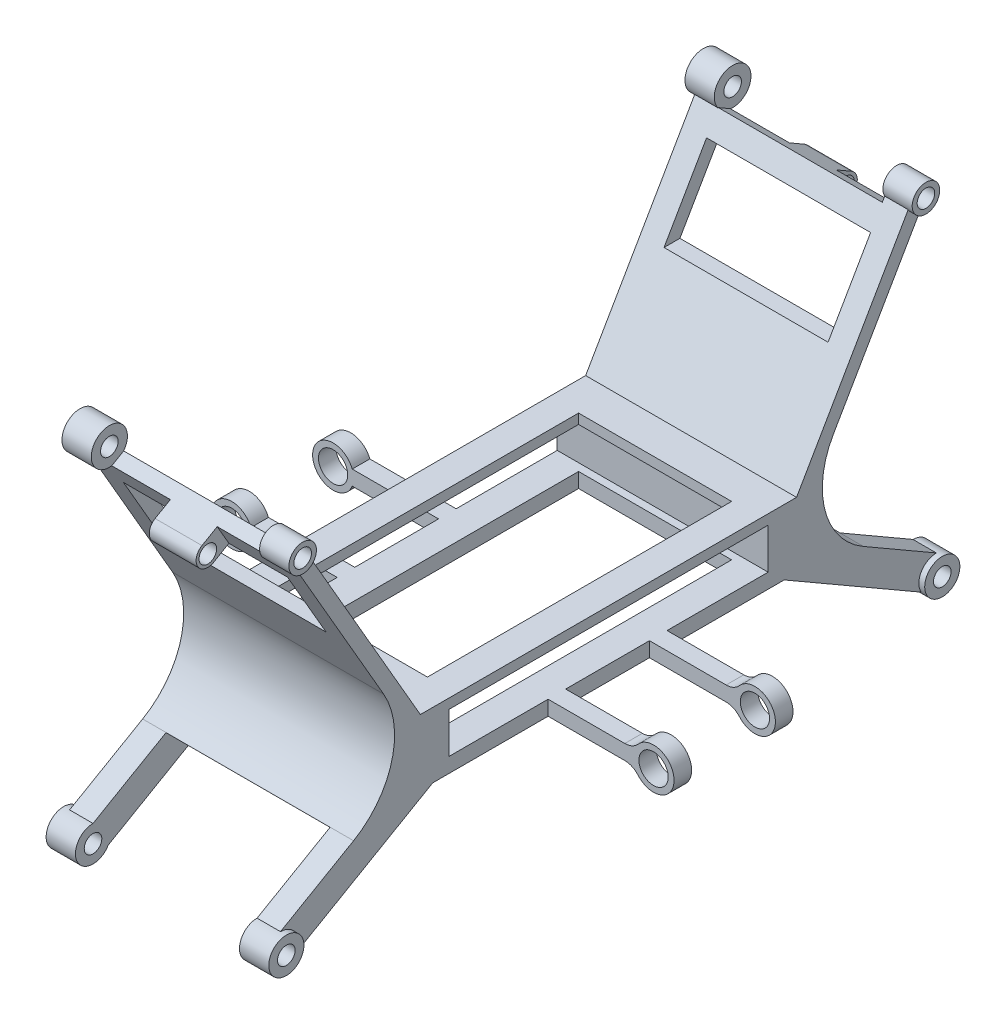
SolidWorks part; units mm, degrees
material "AISI 1020"
ref_plane "Front Plane" through (0, 0, 0) normal (0, 0, 1) x (1, 0, 0)
ref_plane "Top Plane" through (0, 0, 0) normal (0, 1, 0) x (1, 0, 0)
ref_plane "Right Plane" through (0, 0, 0) normal (1, 0, 0) x (0, 0, -1)
sketch "Sketch1" plane through (0, 0, 0) normal (1, 0, 0) x (0, 0, -1)
  line L0 (0, 0) -> (-300, 0)
  line L1 (0, 0) -> (300, 0)
  line L2 (-300, 0) -> (-559.8076, -150)
  line L3 (300, 0) -> (559.8076, -150)
  line L4 (-559.8076, -150) -> (-559.8076, -90)
  line L5 (559.8076, -150) -> (559.8076, -90)
  line L6 (-559.8076, -90) -> (-435.0569, -17.9751)
  line L7 (559.8076, -90) -> (435.0569, -17.9751)
  line L10 (-321.0542, 111.5864) -> (-531.9367, 476.8456)
  line L11 (321.0542, 111.5864) -> (531.9367, 476.8456)
  line L12 (-531.9367, 476.8456) -> (-531.9367, 429.8257)
  line L13 (-531.9367, 429.8257) -> (-383.8133, 173.2684)
  line L14 (531.9367, 476.8456) -> (531.9367, 429.8257)
  line L15 (531.9367, 429.8257) -> (383.8133, 173.2684)
  line L16 (-321.0542, 111.5864) -> (321.0542, 111.5864)
  arc A0 (435.0569, -17.9751) -> (383.8133, 173.2684) centre (505.0569, 103.2684) cw
  arc A1 (-435.0569, -17.9751) -> (-383.8133, 173.2684) centre (-505.0569, 103.2684) ccw
  point P20 (-313.8133, 52.0249)
  dimension "D12" = 140
  dimension "D19" = 0
  dimension "D1" = 300
  dimension "D2" = 300
  dimension "D3" = 300
  dimension "D4" = 300
  dimension "D5" = 30
  dimension "D6" = 30
  dimension "D7" = 60
  dimension "D8" = 60
  dimension "D9" = 60
  dimension "D10" = 51.9615
  dimension "D11" = 60
  dimension "D13" = 60
  dimension "D15" = 0
  dimension "D16" = 60
  dimension "D17" = 0
  dimension "D18" = 0
  dimension "D21" = 144.0498
extrude "Boss-Extrude2" add sketch "Sketch1" along normal blind 360
sketch "Sketch3" plane through (360, 0, 0) normal (1, 0, 0) x (0, 0, -1)
  line L1 (-272.5533, 94.7666) -> (272.5533, 94.7666)
  line L2 (-272.5533, 94.7666) -> (-272.5533, 25.2334)
  line L3 (-272.5533, 25.2334) -> (272.5533, 25.2334)
  line L4 (272.5533, 94.7666) -> (272.5533, 25.2334)
  line L5 (-272.5533, 94.7666) -> (272.5533, 25.2334) construction
  line L6 (-272.5533, 25.2334) -> (272.5533, 94.7666) construction
  point P0 (0, 60)
  dimension "D1" = 60
extrude "Cut-Extrude1" cut sketch "Sketch3" against normal blind 360
sketch "Sketch4" plane through (0, 111.5864, 0) normal (0, 1, 0) x (1, 0, 0)
  line L1 (49.3801, 259.6185) -> (310.6199, 259.6185)
  line L2 (49.3801, 259.6185) -> (49.3801, -259.6185)
  line L3 (49.3801, -259.6185) -> (310.6199, -259.6185)
  line L4 (310.6199, 259.6185) -> (310.6199, -259.6185)
  line L5 (49.3801, 259.6185) -> (310.6199, -259.6185) construction
  line L6 (49.3801, -259.6185) -> (310.6199, 259.6185) construction
  point P0 (180, 0)
extrude "Cut-Extrude2" cut sketch "Sketch4" against normal through all
sketch "Sketch5" plane through (0, 0, -559.8076) normal (0, 0, -1) x (-1, 0, 0)
  line L1 (-360, -90) -> (0, -90) construction
  line L2 (-320, -90) -> (-320, -18.0684)
  line L3 (-320, -18.0684) -> (-40, -18.0684)
  line L4 (-40, -18.0684) -> (-40, -90)
  line L6 (-320, -90) -> (-320, -150)
  line L7 (-360, -150) -> (0, -150) construction
  line L8 (-320, -150) -> (-40, -150)
  line L9 (-40, -150) -> (-40, -90)
  line L10 (-320, 476.8456) -> (-320, 274.0059)
  line L11 (-360, 476.8456) -> (0, 476.8456) construction
  line L12 (-320, 274.0059) -> (-40, 274.0059)
  line L13 (-40, 274.0059) -> (-40, 476.8456)
  line L14 (-40, 476.8456) -> (-320, 476.8456)
  dimension "D1" = 40
  dimension "D2" = 40
extrude "Cut-Extrude4" cut sketch "Sketch5" against normal through all both and the other way through all
sketch "Sketch6" plane through (0, -122.8789, 212.8325) normal (0, -0.5, 0.866) x (1, 0, 0)
  line L0 (40, 630.0084) -> (320, 630.0084)
  line L1 (40, 458.2831) -> (40, 638.2084) construction
  line L2 (320, 638.2084) -> (320, 458.2831) construction
  line L3 (40, 590.0084) -> (320, 590.0084)
  line L4 (40, 630.0084) -> (40, 590.0084)
  line L5 (320, 630.0084) -> (320, 590.0084)
  dimension "D1" = 40
  dimension "D2" = 8.2
extrude "Boss-Extrude3" add sketch "Sketch6" against normal up to vertex (23.5099 mm away) up to point (40, 476.8456, 531.9367)
sketch "Sketch8" plane through (0, -122.8789, -212.8325) normal (0, -0.5, -0.866) x (-1, 0, 0)
  line L0 (-320, 630.0084) -> (-40, 630.0084)
  line L1 (-320, 458.2831) -> (-320, 638.2084) construction
  line L2 (-40, 638.2084) -> (-40, 458.2831) construction
  line L3 (-320, 590.0084) -> (-40, 590.0084)
  line L4 (-320, 630.0084) -> (-320, 590.0084)
  line L5 (-40, 630.0084) -> (-40, 590.0084)
  dimension "D1" = 8.2
  dimension "D2" = 40
extrude "Boss-Extrude4" add sketch "Sketch8" against normal up to vertex (23.5099 mm away) up to point (320, 476.8456, -531.9367)
sketch "Sketch9" plane through (0, -122.8789, -212.8325) normal (0, -0.5, -0.866) x (-1, 0, 0)
  line L0 (-320, 590.0084) -> (-40, 590.0084) construction
  line L1 (-220.9388, 630.0084) -> (-140.9388, 630.0084)
  line L2 (-220.9388, 630.0084) -> (-220.9388, 590.0084)
  line L3 (-220.9388, 590.0084) -> (-140.9388, 590.0084)
  line L4 (-140.9388, 630.0084) -> (-140.9388, 590.0084)
  line L5 (-220.9388, 630.0084) -> (-140.9388, 590.0084) construction
  line L6 (-220.9388, 590.0084) -> (-140.9388, 630.0084) construction
  point P0 (-180.9388, 610.0084)
  dimension "D1" = 40
  dimension "D2" = 40
extrude "Boss-Extrude5" add sketch "Sketch9" along normal blind 30
sketch "Sketch10" plane through (0, -122.8789, 212.8325) normal (0, -0.5, 0.866) x (1, 0, 0)
  line L0 (320, 630.0084) -> (40, 630.0084) construction
  line L1 (140, 590.0084) -> (220, 590.0084)
  line L2 (140, 590.0084) -> (140, 630.0084)
  line L3 (140, 630.0084) -> (220, 630.0084)
  line L4 (220, 590.0084) -> (220, 630.0084)
  line L5 (140, 590.0084) -> (220, 630.0084) construction
  line L6 (140, 630.0084) -> (220, 590.0084) construction
  point P0 (180, 610.0084)
  dimension "D1" = 40
  dimension "D2" = 40
extrude "Boss-Extrude6" add sketch "Sketch10" along normal blind 30
sketch "Sketch13" plane through (220.9388, 0, 0) normal (1, 0, 0) x (0, 0, -1)
  line L0 (553.8175, 407.7243) -> (533.8175, 373.0833) construction
  circle A0 centre (543.8175, 390.4038) radius 20
extrude "Boss-Extrude8" add sketch "Sketch13" against normal up to vertex (80 mm away) up to point (140.9388, 373.0833, -533.8175)
sketch "Sketch14" plane through (220.9388, 0, 0) normal (1, 0, 0) x (0, 0, -1)
  circle A0 centre (543.8175, 390.4038) radius 15
  dimension "D1" = 30
extrude "Cut-Extrude5" cut sketch "Sketch14" against normal through all and the other way through all
sketch "Sketch15" plane through (220, 0, 0) normal (1, 0, 0) x (0, 0, -1)
  line L0 (-533.8175, 373.0833) -> (-553.8175, 407.7243) construction
  circle A0 centre (-543.8175, 390.4038) radius 20
extrude "Boss-Extrude9" add sketch "Sketch15" against normal up to vertex (80 mm away) up to point (140, 373.0833, 533.8175)
sketch "Sketch16" plane through (220, 0, 0) normal (1, 0, 0) x (0, 0, -1)
  circle A0 centre (-543.8175, 390.4038) radius 15
  dimension "D1" = 30
extrude "Cut-Extrude6" cut sketch "Sketch16" against normal through all
sketch "Sketch17" plane through (360, 0, 0) normal (1, 0, 0) x (0, 0, -1)
  line L0 (-559.8076, -90) -> (-559.8076, -150) construction
  circle A0 centre (-559.8076, -120) radius 30
extrude "Boss-Extrude10" add sketch "Sketch17" against normal up to vertex (40 mm away) and the other way blind 10 up to point (320, -150, 559.8076)
sketch "Sketch18" plane through (0, 0, 0) normal (-1, 0, 0) x (0, 0, 1)
  circle A0 centre (559.8076, -120) radius 30
extrude "Boss-Extrude11" add sketch "Sketch18" against normal up to vertex (40 mm away) and the other way blind 10 up to point (40, -90, 559.8076)
sketch "Sketch19" plane through (360, 0, 0) normal (1, 0, 0) x (0, 0, -1)
  line L0 (559.8076, -150) -> (559.8076, -90) construction
  circle A0 centre (559.8076, -120) radius 30
extrude "Boss-Extrude12" add sketch "Sketch19" against normal up to vertex (40 mm away) and the other way blind 10 up to point (320, -150, -559.8076)
sketch "Sketch20" plane through (0, 0, 0) normal (-1, 0, 0) x (0, 0, 1)
  line L0 (-559.8076, -150) -> (-559.8076, -90) construction
  circle A0 centre (-559.8076, -120) radius 30
extrude "Boss-Extrude13" add sketch "Sketch20" against normal up to vertex (40 mm away) and the other way blind 10 up to point (40, -90, -559.8076)
sketch "Sketch21" plane through (370, 0, 0) normal (1, 0, 0) x (0, 0, -1)
  circle A0 centre (559.8076, -120) radius 15
  dimension "D1" = 30
extrude "Cut-Extrude7" cut sketch "Sketch21" against normal through all
sketch "Sketch22" plane through (370, 0, 0) normal (1, 0, 0) x (0, 0, -1)
  circle A0 centre (-559.8076, -120) radius 15
  dimension "D1" = 30
extrude "Cut-Extrude8" cut sketch "Sketch22" against normal through all
sketch "Sketch23" plane through (360, 0, 0) normal (1, 0, 0) x (0, 0, -1)
  line L0 (-531.9367, 476.8456) -> (-531.9367, 429.8257) construction
  circle A0 centre (-531.9367, 453.3357) radius 23.5099
extrude "Boss-Extrude14" add sketch "Sketch23" against normal up to vertex (40 mm away) and the other way blind 10 up to point (320, 476.8456, 531.9367)
sketch "Sketch24" plane through (0, 0, 0) normal (-1, 0, 0) x (0, 0, 1)
  line L0 (531.9367, 476.8456) -> (531.9367, 429.8257) construction
  circle A0 centre (531.9367, 453.3357) radius 30.8745
extrude "Boss-Extrude15" add sketch "Sketch24" against normal up to vertex (40 mm away) and the other way blind 10 up to point (40, 429.8257, 531.9367)
sketch "Sketch25" plane through (360, 0, 0) normal (1, 0, 0) x (0, 0, -1)
  line L0 (531.9367, 429.8257) -> (531.9367, 476.8456) construction
  circle A0 centre (531.9367, 453.3357) radius 23.5099
extrude "Boss-Extrude16" add sketch "Sketch25" against normal up to vertex (40 mm away) and the other way blind 10 up to point (320, 429.8257, -531.9367)
sketch "Sketch26" plane through (0, 0, 0) normal (-1, 0, 0) x (0, 0, 1)
  line L0 (-531.9367, 429.8257) -> (-531.9367, 476.8456) construction
  circle A0 centre (-531.9367, 453.3357) radius 31.3316
extrude "Boss-Extrude17" add sketch "Sketch26" against normal up to vertex (40 mm away) and the other way blind 10 up to point (40, 476.8456, -531.9367)
sketch "Sketch27" plane through (-10, 0, 0) normal (-1, 0, 0) x (0, 0, 1)
  circle A0 centre (-531.9367, 453.3357) radius 15
  dimension "D1" = 30
extrude "Cut-Extrude9" cut sketch "Sketch27" against normal through all
sketch "Sketch28" plane through (-10, 0, 0) normal (-1, 0, 0) x (0, 0, 1)
  circle A0 centre (531.9367, 453.3357) radius 15
  dimension "D1" = 30
extrude "Cut-Extrude10" cut sketch "Sketch28" against normal through all
sketch "Sketch30" plane through (360, 0, 0) normal (1, 0, 0) x (0, 0, -1)
  line L0 (-73.0192, 25.2334) -> (-73.0192, 0)
  line L1 (-272.5533, 25.2334) -> (272.5533, 25.2334) construction
  line L2 (-300, 0) -> (300, 0) construction
  line L3 (-73.0192, 0) -> (-103.0192, 0)
  line L4 (-103.0192, 0) -> (-103.0192, 25.2334)
  line L5 (-103.0192, 25.2334) -> (-73.0192, 25.2334)
  line L6 (70, 25.2334) -> (70, 0)
  line L7 (70, 0) -> (100, 0)
  line L8 (100, 0) -> (100, 25.2334)
  line L9 (100, 25.2334) -> (70, 25.2334)
  dimension "D1" = 73.0192
  dimension "D2" = 70
  dimension "D3" = 30
  dimension "D4" = 30
extrude "Boss-Extrude18" add sketch "Sketch30" along normal blind 180
sketch "Sketch31" plane through (0, 0, 103.0192) normal (0, 0, 1) x (1, 0, 0)
  line L0 (540, 25.2334) -> (540, 0) construction
  circle A0 centre (540, 12.6167) radius 35
  dimension "D1" = 70
extrude "Boss-Extrude19" add sketch "Sketch31" against normal up to vertex (30 mm away) up to point (540, 25.2334, 73.0192)
sketch "Sketch32" plane through (0, 0, -100) normal (0, 0, -1) x (-1, 0, 0)
  line L0 (-540, 0) -> (-540, 25.2334) construction
  circle A0 centre (-540, 12.6167) radius 35
  dimension "D1" = 70
extrude "Boss-Extrude20" add sketch "Sketch32" against normal up to vertex (30 mm away) up to point (540, 0, -70)
sketch "Sketch33" plane through (0, 0, 103.0192) normal (0, 0, 1) x (1, 0, 0)
  circle A0 centre (540, 12.6167) radius 25
  dimension "D1" = 50
extrude "Cut-Extrude11" cut sketch "Sketch33" against normal through all
fillet "Fillet1" radius 30 4 edges at (507.3531, 0, 88.0192) (507.3531, 0, -85) (507.3531, 25.2334, 88.0192) (507.3531, 25.2334, -85)
sketch "Sketch34" plane through (0, 0, 0) normal (-1, 0, 0) x (0, 0, 1)
  line L4 (-70, 0) -> (-70, 25.2334)
  line L5 (-100, 0) -> (-70, 0)
  line L6 (-100, 25.2334) -> (-100, 0)
  line L7 (-70, 25.2334) -> (-100, 25.2334)
  line L8 (-70, 0) -> (-70, 25.2334)
  line L9 (-100, 0) -> (-70, 0)
  line L10 (-100, 25.2334) -> (-100, 0)
  line L11 (-70, 25.2334) -> (-100, 25.2334)
  line L12 (73.0192, 25.2334) -> (73.0192, 0)
  line L13 (73.0192, 0) -> (103.0192, 0)
  line L14 (103.0192, 0) -> (103.0192, 25.2334)
  line L15 (103.0192, 25.2334) -> (73.0192, 25.2334)
  line L16 (73.0192, 25.2334) -> (73.0192, 0)
  line L17 (73.0192, 0) -> (103.0192, 0)
  line L18 (103.0192, 0) -> (103.0192, 25.2334)
  line L19 (103.0192, 25.2334) -> (73.0192, 25.2334)
  dimension "D1" = 0
  dimension "D2" = 0
extrude "Boss-Extrude21" add sketch "Sketch34" along normal blind 180
sketch "Sketch35" plane through (0, 0, 103.0192) normal (0, 0, 1) x (1, 0, 0)
  line L1 (-180, 0) -> (-180, 25.2334) construction
  circle A0 centre (-180, 12.6167) radius 35
  dimension "D1" = 70
extrude "Boss-Extrude22" add sketch "Sketch35" against normal up to vertex (30 mm away) up to point (-180, 25.2334, 73.0192)
sketch "Sketch36" plane through (0, 0, -100) normal (0, 0, -1) x (-1, 0, 0)
  line L0 (180, 25.2334) -> (180, 0) construction
  circle A0 centre (180, 12.6167) radius 35
extrude "Boss-Extrude23" add sketch "Sketch36" against normal up to vertex (30 mm away) up to point (-180, 25.2334, -70)
sketch "Sketch37" plane through (0, 0, -100) normal (0, 0, -1) x (-1, 0, 0)
  circle A0 centre (180, 12.6167) radius 25
  dimension "D1" = 50
extrude "Cut-Extrude12" cut sketch "Sketch37" against normal through all
